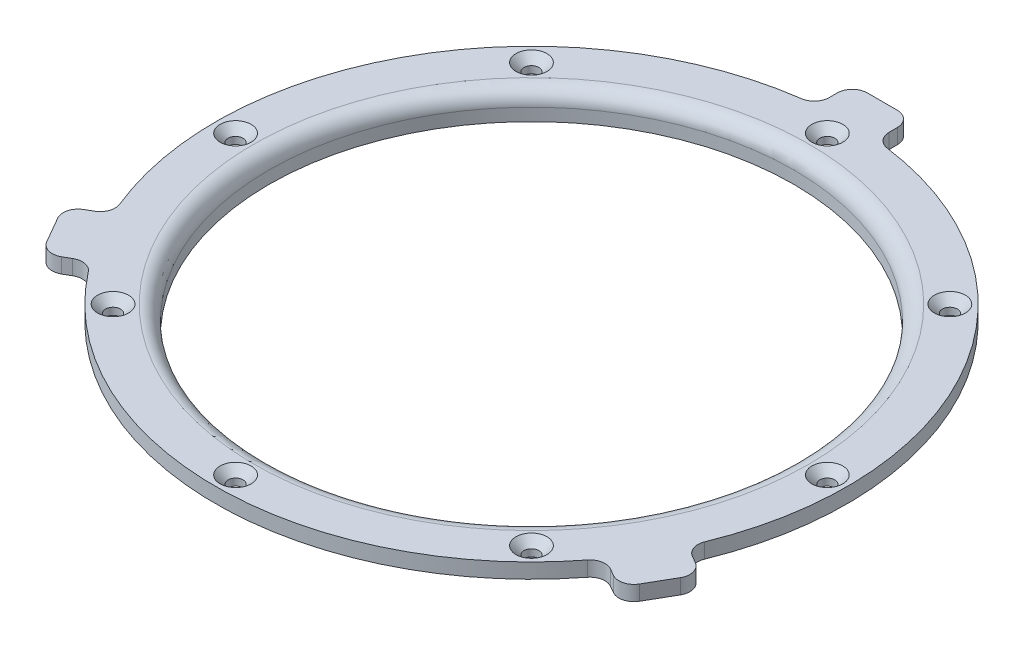
SolidWorks part; units mm, degrees
material "PET"
ref_plane "Front Plane" through (0, 0, 0) normal (0, 0, 1) x (1, 0, 0)
ref_plane "Top Plane" through (0, 0, 0) normal (0, 1, 0) x (1, 0, 0)
ref_plane "Right Plane" through (0, 0, 0) normal (1, 0, 0) x (0, 0, -1)
sketch "Sketch2" plane through (0, 0, 0) normal (0, 0, 1) x (1, 0, 0)
  line L0 (-55, 9.3) -> (-52.5, 9.3)
  line L1 (-52.5, 9.3) -> (-52.5, 14.8)
  line L2 (-52.5, 14.8) -> (-63.2, 14.8)
  line L3 (-63.2, 14.8) -> (-63.2, 11.8)
  line L4 (-63.2, 11.8) -> (-55, 11.8)
  line L5 (-55, 11.8) -> (-55, 9.3)
  line L11 (0, 0) -> (0, 30.013) construction
sketch "Sketch3" plane through (0, 0, 0) normal (0, 0, 1) x (1, 0, 0)
  line L6 (-55, 9.3) -> (-52.5, 9.3)
  line L7 (-52.5, 9.3) -> (-52.5, 14.8)
  line L8 (-52.5, 14.8) -> (-63.2, 14.8)
  line L9 (-63.2, 14.8) -> (-63.2, 11.8)
  line L10 (-63.2, 11.8) -> (-55, 11.8)
  line L11 (-55, 11.8) -> (-55, 9.3)
  line L12 (-55, 9.3) -> (-52.5, 9.3)
  line L13 (-52.5, 9.3) -> (-52.5, 14.8)
  line L14 (-52.5, 14.8) -> (-63.2, 14.8)
  line L15 (-63.2, 14.8) -> (-63.2, 11.8)
  line L16 (-63.2, 11.8) -> (-55, 11.8)
  line L17 (-55, 11.8) -> (-55, 9.3)
  dimension "D1" = 0
revolve "Cap" add sketch "Sketch3" angle 360 about L11
sketch "Sketch9" plane through (0, 0, 0) normal (0, 0, 1) x (1, 0, 0)
  line L0 (-63.2, 11.8) -> (-55.2, 11.8) construction
  line L4 (-59.2, 11.8) -> (-59.2, 0.8)
  line L5 (-59.2, 11.8) -> (-57.95, 11.8)
  line L6 (-59.2, 11.8) -> (-57.1, 11.8)
  point P3 (-59.2, 11.8)
sketch "Sketch10" plane through (0, 0, 0) normal (0, 1, 0) x (1, 0, 0)
  circle A0 centre (-59.2, 0) radius 2.1
  point P0 (-59.2, 0)
  point P1 (-57.1, 0)
hole_wizard "CSK for M3 Flat Head Machine Screw1" positions "Sketch11" profile "Sketch12" countersink size "M3" standard "ANSI Metric"
sketch "Sketch11" plane through (0, 14.8, 0) normal (0, 1, 0) x (1, 0, 0)
  point P0 (-59.2, 0)
sketch "Sketch12" plane through (-59.2, 14.8, 0) normal (1, 0, 0) x (0, 0, 1)
  line L0 (0, 0) -> (0, 9.7913)
  line L1 (0, 9.7913) -> (1.5, 8.89)
  line L2 (1.5, 8.89) -> (1.5, 1.6)
  line L3 (1.5, 1.6) -> (3.1, 0)
  line L5 (3.1, 0) -> (0, 0)
  line L6 (-1.5, 1.6) -> (-3.1, 0) construction
  line L10 (0, 9.7913) -> (-1.5, 8.89) construction
  line L11 (0, -6.35) -> (0, 107.95) construction
  dimension "Hole Dia." = 3
  dimension "Hole Depth" = 8.89
  dimension "Near C'Sink Dia." = 6.2
  dimension "Near C'Sink Angle" = 90
  dimension "Drill Angle" = 118
pattern_circular "CirPattern1" count 8 over 360 about axis through (0, 0, 0) along (0, 1, 0) of "CSK for M3 Flat Head Machine Screw1" reverse direction yes
fillet "Fillet1" radius 3 1 edges at (52.5, 14.8, 0)
sketch "Sketch13" plane through (0, 0, 0) normal (0, 0, 1) x (1, 0, 0)
  line L0 (-63.4027, 9.8) -> (-70.2, 9.8)
  line L2 (-70.2, 9.8) -> (-70.2, -3.2)
  line L3 (-70.2, -3.2) -> (-63.4027, -3.2)
  line L4 (-63.4027, -3.2) -> (-63.4027, 9.8)
  line L6 (0, 0) -> (0, 30.013) construction
sketch "Sketch14" plane through (0, 0, 0) normal (0, 1, 0) x (1, 0, 0)
  line L0 (-70.2, 0) -> (-63.4027, 0) construction
  line L1 (-70.2, 0) -> (-63.4027, 0) construction
  line L2 (-63.4027, 0) -> (-70.2, 0) construction
  line L3 (-63.795, -29.9038) -> (-57.795, -40.2962)
  line L4 (-63.795, -29.9038) -> (-57.4856, -26.2611)
  line L5 (-57.795, -40.2962) -> (-51.4856, -36.6534)
  line L6 (-57.4856, -26.2611) -> (-51.4856, -36.6534)
  point P5 (-60.795, -35.1)
  dimension "D1" = 12
extrude "Boss-Extrude1" add sketch "Sketch14" against normal up to surface (-11.8 mm away) from surface up to face at (-43.3607, 11.8, 41.8607) starting at face at (55.5, 14.8, 0)
fillet "Fillet2" radius 3 4 edges at (-57.4856, 13.3, 26.2611) (-63.795, 13.3, 29.9038) (-57.795, 13.3, 40.2962) (-51.4856, 13.3, 36.6534)
pattern_circular "CirPattern2" count 3 over 360 about axis through (0, 0, 0) along (0, 1, 0) of "Boss-Extrude1", "Fillet2" reverse direction yes
equation "\"TopHoles\"= 8"
equation "\"D1@CirPattern1\"=\"TopHoles\""
